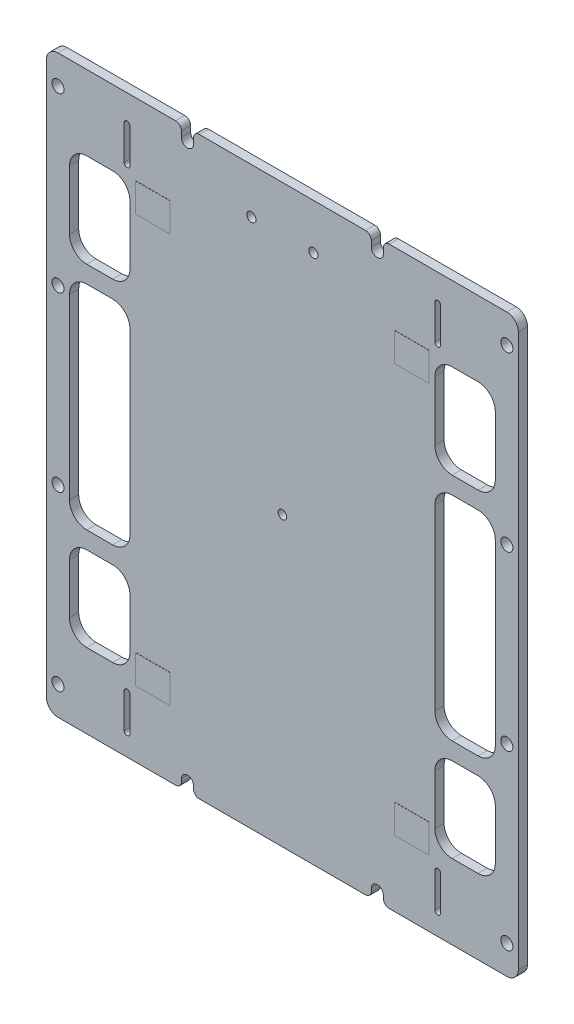
SolidWorks part; units mm, degrees
material "FR4_stuffedProtoboard"
ref_plane "Front Plane" through (0, 0, 0) normal (0, 0, 1) x (1, 0, 0)
ref_plane "Top Plane" through (0, 0, 0) normal (0, 1, 0) x (1, 0, 0)
ref_plane "Right Plane" through (0, 0, 0) normal (1, 0, 0) x (0, 0, -1)
sketch "Sketch1" plane through (0, 0, 0) normal (0, 0, 1) x (1, 0, 0)
  line L1 (-39, -50) -> (39, -50)
  line L2 (-41, -48) -> (-41, 48)
  line L3 (-39, 50) -> (39, 50)
  line L4 (41, -48) -> (41, 48)
  line L5 (-41, -50) -> (41, 50) construction
  line L6 (-41, 50) -> (41, -50) construction
  arc A0 (-39, -50) -> (-41, -48) centre (-39, -48) cw
  arc A1 (39, -50) -> (41, -48) centre (39, -48) ccw
  arc A2 (39, 50) -> (41, 48) centre (39, 48) cw
  arc A3 (-41, 48) -> (-39, 50) centre (-39, 48) cw
  point P0 (0, 0)
  dimension "D3" = 2
  dimension "D1" = 100
  dimension "D2" = 82
extrude "boardOutline" add sketch "Sketch1" along normal blind 1.6
sketch "Sketch2" plane through (0, 0, 1.6) normal (0, 0, 1) x (1, 0, 0)
  line L0 (39, 50) -> (-39, 50) construction
  line L1 (-41, 48) -> (-41, -48) construction
  line L2 (-5.385, 42.1) -> (5.385, 42.1) construction
  line L3 (-37.5, 44.2) -> (-37.5, 4.2) construction
  line L4 (0, 42.1) -> (0, 50) construction
  circle A0 centre (0, 0) radius 0.75
  circle A1 centre (-37.5, 44.2) radius 1.05 construction
  circle A2 centre (37.5, 44.2) radius 1.05 construction
  circle A3 centre (37.5, 4.2) radius 1.05 construction
  circle A4 centre (37.5, -35.8) radius 1.05 construction
  circle A5 centre (-37.5, 4.2) radius 1.05 construction
  circle A6 centre (-37.5, -35.8) radius 1.05 construction
  circle A7 centre (-5.385, 42.1) radius 0.8
  circle A8 centre (5.385, 42.1) radius 0.8
  dimension "D1" = 1.5
  dimension "D2" = 2.1
  dimension "D9" = 10.77
  dimension "D7" = 1.6
  dimension "D11" = 7.9
  dimension "D3" = 5.8
  dimension "D4" = 3.5
  dimension "D8" = 40
  dimension "D10" = 37.5
  dimension "D5" = 2
  dimension "D6" = 3
extrude "componentHoles" cut sketch "Sketch2" against normal through all
sketch "Sketch4" plane through (0, 0, 1.6) normal (0, 0, 1) x (1, 0, 0)
  line L0 (-27, 39.25) -> (-27, 45.25) construction
  line L1 (-27.5, 39.25) -> (-27.5, 45.25)
  line L2 (-26.5, 39.25) -> (-26.5, 45.25)
  line L3 (39, 50) -> (-39, 50) construction
  line L4 (-41, 48) -> (-41, -48) construction
  line L5 (27, 39.25) -> (27, 45.25) construction
  line L6 (26.5, 39.25) -> (26.5, 45.25)
  line L7 (27.5, 39.25) -> (27.5, 45.25)
  line L8 (27, -46.25) -> (27, -40.25) construction
  line L9 (26.5, -46.25) -> (26.5, -40.25)
  line L10 (27.5, -46.25) -> (27.5, -40.25)
  line L11 (-27, -46.25) -> (-27, -40.25) construction
  line L12 (-27.5, -46.25) -> (-27.5, -40.25)
  line L13 (-26.5, -46.25) -> (-26.5, -40.25)
  line L14 (-27, 39.25) -> (27, 39.25) construction
  line L15 (0, 39.25) -> (0, 50) construction
  arc A0 (-27.5, 39.25) -> (-26.5, 39.25) centre (-27, 39.25) ccw
  arc A1 (-26.5, 45.25) -> (-27.5, 45.25) centre (-27, 45.25) ccw
  arc A2 (26.5, 39.25) -> (27.5, 39.25) centre (27, 39.25) ccw
  arc A3 (27.5, 45.25) -> (26.5, 45.25) centre (27, 45.25) ccw
  arc A4 (26.5, -46.25) -> (27.5, -46.25) centre (27, -46.25) ccw
  arc A5 (27.5, -40.25) -> (26.5, -40.25) centre (27, -40.25) ccw
  arc A6 (-27.5, -46.25) -> (-26.5, -46.25) centre (-27, -46.25) ccw
  arc A7 (-26.5, -40.25) -> (-27.5, -40.25) centre (-27, -40.25) ccw
  point P2 (-27, 42.25)
  point P16 (27, 42.25)
  point P23 (27, -43.25)
  point P30 (-27, -43.25)
  dimension "D1" = 4.75
  dimension "D2" = 13.5
  dimension "D3" = 1
  dimension "D4" = 6
  dimension "D7" = 54
  dimension "D9" = 79.5
  dimension "D5" = 2
  dimension "D6" = 2
extrude "solarCellContactHoles" cut sketch "Sketch4" against normal blind 1.6
sketch "Sketch3" plane through (0, 0, 1.6) normal (0, 0, 1) x (1, 0, 0)
  line L1 (-34, 37) -> (-29.5, 37)
  line L2 (-37, 34) -> (-37, 23.7)
  line L3 (-34, 20.7) -> (-29.5, 20.7)
  line L4 (-26.5, 34) -> (-26.5, 23.7)
  line L5 (-41, 48) -> (-41, -48) construction
  line L6 (-29.5, -22.3) -> (-34, -22.3)
  line L9 (0, 50) -> (0, -50) construction
  line L10 (39, 50) -> (-39, 50) construction
  line L11 (-39, -50) -> (39, -50) construction
  line L12 (-26.5, -25.3) -> (-26.5, -34)
  line L13 (-29.5, -37) -> (-34, -37)
  line L14 (-37, -25.3) -> (-37, -34)
  line L19 (-29.5, -19.3) -> (-34, -19.3)
  line L25 (-26.5, -16.3) -> (-26.5, 14.7)
  line L26 (-29.5, 17.7) -> (-34, 17.7)
  line L27 (-37, -16.3) -> (-37, 14.7)
  arc A0 (-37, 23.7) -> (-34, 20.7) centre (-34, 23.7) ccw
  arc A1 (-29.5, 20.7) -> (-26.5, 23.7) centre (-29.5, 23.7) ccw
  arc A2 (-29.5, 37) -> (-26.5, 34) centre (-29.5, 34) cw
  arc A3 (-34, 37) -> (-37, 34) centre (-34, 34) ccw
  arc A4 (-29.5, -19.3) -> (-26.5, -16.3) centre (-29.5, -16.3) ccw
  arc A5 (-26.5, -34) -> (-29.5, -37) centre (-29.5, -34) cw
  arc A6 (-34, -37) -> (-37, -34) centre (-34, -34) cw
  arc A7 (-34, -22.3) -> (-37, -25.3) centre (-34, -25.3) ccw
  arc A8 (-29.5, -22.3) -> (-26.5, -25.3) centre (-29.5, -25.3) cw
  arc A17 (-34, -19.3) -> (-37, -16.3) centre (-34, -16.3) cw
  arc A18 (-34, 17.7) -> (-37, 14.7) centre (-34, 14.7) ccw
  arc A19 (-26.5, 14.7) -> (-29.5, 17.7) centre (-29.5, 14.7) ccw
  point P12 (-26.5, 20.7)
  point P15 (-26.5, 37)
  point P18 (-37, 37)
  dimension "D5" = 3
  dimension "D10" = 13
  dimension "D7" = 3
  dimension "D11" = 3
  dimension "D1" = 10.5
  dimension "D2" = 29.3
  dimension "D3" = 13
  dimension "D4" = 4
  dimension "D8" = 3
  dimension "D9" = 3
  dimension "D6" = 37
extrude "windows_1side" cut sketch "Sketch3" against normal through all
sketch "Sketch5" plane through (0, 0, 1.6) normal (0, 0, 1) x (1, 0, 0)
  line L0 (-41, 48) -> (-41, -48) construction
  line L1 (-25.5, 37.5) -> (-19.5, 37.5)
  line L2 (-25.5, 37.5) -> (-25.5, 32.5)
  line L3 (-25.5, 32.5) -> (-19.5, 32.5)
  line L4 (-19.5, 37.5) -> (-19.5, 32.5)
  line L5 (0, 37.5) -> (0, 50) construction
  line L6 (19.5, 37.5) -> (19.5, 32.5)
  line L7 (25.5, 37.5) -> (25.5, 32.5)
  line L8 (19.5, 32.5) -> (25.5, 32.5)
  line L9 (19.5, 37.5) -> (25.5, 37.5)
  line L10 (19.5, -33.5) -> (19.5, -38.5)
  line L11 (25.5, -33.5) -> (25.5, -38.5)
  line L12 (19.5, -38.5) -> (25.5, -38.5)
  line L13 (19.5, -33.5) -> (25.5, -33.5)
  line L14 (-25.5, -33.5) -> (-25.5, -38.5)
  line L15 (-19.5, -33.5) -> (-19.5, -38.5)
  line L16 (-25.5, -38.5) -> (-19.5, -38.5)
  line L17 (-25.5, -33.5) -> (-19.5, -33.5)
  line L18 (-19.5, 37.5) -> (19.5, 37.5) construction
  line L19 (-25.5, 37.5) -> (-25.5, -33.5) construction
  line L20 (39, 50) -> (-39, 50) construction
  arc A0 (-27.5, 39.25) -> (-26.5, 39.25) centre (-27, 39.25) ccw construction
  dimension "D1" = 5
  dimension "D2" = 6
  dimension "D3" = 15.5
  dimension "D4" = 1.75
  dimension "D7" = 45
  dimension "D8" = 71
  dimension "D5" = 2
  dimension "D6" = 2
extrude "contactPads" add sketch "Sketch5" along normal blind 0.02
hole_wizard "M2 Clearance Hole1" positions "Sketch6" profile "Sketch7" hole size "M2" standard "ANSI Metric" end condition through all
sketch "Sketch6" plane through (0, 0, 0) normal (0, 0, -1) x (-1, 0, 0)
  line L5 (39, -50) -> (39, -45) construction
  line L6 (39, -50) -> (-39, -50) construction
  line L7 (39, -45) -> (39, -15) construction
  line L8 (39, -15) -> (39, 15) construction
  line L9 (39, 15) -> (39, 45) construction
  line L10 (39, 45) -> (39, 50) construction
  line L11 (-39, 50) -> (39, 50) construction
  line L15 (37, -27.0602) -> (41, -27.0602) construction
  line L16 (37, -25.3) -> (37, -34) construction
  line L17 (41, 48) -> (41, -48) construction
  point P0 (39, 45)
  point P27 (39, -15)
  point P36 (39, -45)
  point P38 (39, 15)
  point P73 (39, -27.0602)
  dimension "D2" = 5
sketch "Sketch7" plane through (-39, 45, 0) normal (1, 0, 0) x (0, 1, 0)
  line L0 (0, 0) -> (0, 1.62)
  line L1 (0, 1.62) -> (1.05, 1.62)
  line L2 (1.05, 1.62) -> (1.05, 0)
  line L5 (1.05, 0) -> (0, 0)
  line L11 (0, -6.35) -> (0, 107.95) construction
  dimension "Thru Hole Dia." = 2.1
  dimension "Thru Hole Depth" = 1.62
sketch "Sketch10" plane through (0, 0, 0) normal (0, 0, -1) x (-1, 0, 0)
  line L0 (16.5, 48) -> (16.5, 55.0732) construction
  line L1 (15.45, 48) -> (15.45, 55.0732)
  line L2 (17.55, 48) -> (17.55, 55.0732)
  line L3 (16.5, -48.5) -> (16.5, -55.5732) construction
  line L4 (17.55, -48.5) -> (17.55, -55.5732)
  line L5 (15.45, -48.5) -> (15.45, -55.5732)
  line L6 (41, 48) -> (41, -48) construction
  line L8 (39, -50) -> (-39, -50) construction
  line L9 (-39, 50) -> (39, 50) construction
  arc A0 (15.45, 48) -> (17.55, 48) centre (16.5, 48) ccw
  arc A1 (17.55, 55.0732) -> (15.45, 55.0732) centre (16.5, 55.0732) ccw
  arc A2 (17.55, -48.5) -> (15.45, -48.5) centre (16.5, -48.5) ccw
  arc A3 (15.45, -55.5732) -> (17.55, -55.5732) centre (16.5, -55.5732) ccw
  point P2 (16.5, 51.5366)
  point P7 (16.5, -52.0366)
  dimension "D1" = 1.05
  dimension "D2" = 24.5
  dimension "D3" = 2
  dimension "D4" = 1.5
extrude "Cut-Extrude1" cut sketch "Sketch10" against normal through all both and the other way through all
fillet "Fillet3" radius 1 4 edges at (-17.55, 50, 0.8) (-15.45, 50, 0.8) (-15.45, -50, 0.8) (-17.55, -50, 0.8)
mirror "Mirror1" about plane through (0, 0, 0) normal (1, 0, 0) of "Cut-Extrude1", "Fillet3", "windows_1side", "M2 Clearance Hole1"
sketch "thermalContact" plane through (0, 0, 1.6) normal (0, 0, 1) x (1, 0, 0)
  line L0 (-37, 43) -> (-37, 23.7) construction
  line L1 (-34, 20.7) -> (-21, 20.7) construction
  line L2 (-18, 23.7) -> (-18, 43) construction
  line L3 (-21, 46) -> (-34, 46) construction
  line L4 (-41, 48) -> (-41, -162)
  line L5 (39, 50) -> (-39, 50)
  line L6 (41, -162) -> (41, 48)
  line L7 (-39, -164) -> (39, -164)
  line L8 (-41, 48) -> (-41, -162)
  line L9 (39, 50) -> (-39, 50)
  line L10 (41, -162) -> (41, 48)
  line L11 (-39, -164) -> (39, -164)
  line L12 (-37, 43) -> (-37, 23.7)
  line L13 (-34, 20.7) -> (-21, 20.7)
  line L14 (-18, 23.7) -> (-18, 43)
  line L15 (-21, 46) -> (-34, 46)
  line L16 (18, 43) -> (18, 23.7) construction
  line L17 (21, 20.7) -> (34, 20.7) construction
  line L18 (37, 23.7) -> (37, 43) construction
  line L19 (34, 46) -> (21, 46) construction
  line L20 (18, 43) -> (18, 23.7)
  line L21 (21, 20.7) -> (34, 20.7)
  line L22 (37, 23.7) -> (37, 43)
  line L23 (34, 46) -> (21, 46)
  line L24 (-12, -47) -> (12, -47) construction
  line L25 (15, -44) -> (15, -25.3) construction
  line L26 (12, -22.3) -> (-12, -22.3) construction
  line L27 (-15, -25.3) -> (-15, -44) construction
  line L28 (-12, -47) -> (12, -47)
  line L29 (15, -44) -> (15, -25.3)
  line L30 (12, -22.3) -> (-12, -22.3)
  line L31 (-15, -25.3) -> (-15, -44)
  line L32 (-37, -25.3) -> (-37, -44) construction
  line L33 (-34, -47) -> (-21, -47) construction
  line L34 (-18, -44) -> (-18, -25.3) construction
  line L35 (-21, -22.3) -> (-34, -22.3) construction
  line L36 (-37, -25.3) -> (-37, -44)
  line L37 (-34, -47) -> (-21, -47)
  line L38 (-18, -44) -> (-18, -25.3)
  line L39 (-21, -22.3) -> (-34, -22.3)
  line L40 (18, -25.3) -> (18, -44) construction
  line L41 (21, -47) -> (34, -47) construction
  line L42 (37, -44) -> (37, -25.3) construction
  line L43 (34, -22.3) -> (21, -22.3) construction
  line L44 (18, -25.3) -> (18, -44)
  line L45 (21, -47) -> (34, -47)
  line L46 (37, -44) -> (37, -25.3)
  line L47 (34, -22.3) -> (21, -22.3)
  line L48 (-12, -19.3) -> (12, -19.3) construction
  line L49 (15, -16.3) -> (15, 14.7) construction
  line L50 (12, 17.7) -> (-12, 17.7) construction
  line L51 (-15, 14.7) -> (-15, -16.3) construction
  line L52 (-12, -19.3) -> (12, -19.3)
  line L53 (15, -16.3) -> (15, 14.7)
  line L54 (12, 17.7) -> (-12, 17.7)
  line L55 (-15, 14.7) -> (-15, -16.3)
  line L56 (-21, 17.7) -> (-34, 17.7) construction
  line L57 (-37, 14.7) -> (-37, -16.3) construction
  line L58 (-34, -19.3) -> (-21, -19.3) construction
  line L59 (-18, -16.3) -> (-18, 14.7) construction
  line L60 (-21, 17.7) -> (-34, 17.7)
  line L61 (-37, 14.7) -> (-37, -16.3)
  line L62 (-34, -19.3) -> (-21, -19.3)
  line L63 (-18, -16.3) -> (-18, 14.7)
  line L64 (21, -19.3) -> (34, -19.3) construction
  line L65 (37, -16.3) -> (37, 14.7) construction
  line L66 (34, 17.7) -> (21, 17.7) construction
  line L67 (18, 14.7) -> (18, -16.3) construction
  line L68 (21, -19.3) -> (34, -19.3)
  line L69 (37, -16.3) -> (37, 14.7)
  line L70 (34, 17.7) -> (21, 17.7)
  line L71 (18, 14.7) -> (18, -16.3)
  line L72 (-12, 20.7) -> (12, 20.7) construction
  line L73 (15, 23.7) -> (15, 43) construction
  line L74 (12, 46) -> (-12, 46) construction
  line L75 (-15, 43) -> (-15, 23.7) construction
  line L76 (-12, 20.7) -> (12, 20.7)
  line L77 (15, 23.7) -> (15, 43)
  line L78 (12, 46) -> (-12, 46)
  line L79 (-15, 43) -> (-15, 23.7)
  line L80 (-21, -50) -> (-34, -50) construction
  line L81 (-37, -53) -> (-37, -61) construction
  line L82 (-34, -64) -> (-21, -64) construction
  line L83 (-18, -61) -> (-18, -53) construction
  line L84 (-21, -50) -> (-34, -50)
  line L85 (-37, -53) -> (-37, -61)
  line L86 (-34, -64) -> (-21, -64)
  line L87 (-18, -61) -> (-18, -53)
  line L88 (-15, -53) -> (-15, -61) construction
  line L89 (-12, -64) -> (12, -64) construction
  line L90 (15, -61) -> (15, -53) construction
  line L91 (12, -50) -> (-12, -50) construction
  line L92 (-15, -53) -> (-15, -61)
  line L93 (-12, -64) -> (12, -64)
  line L94 (15, -61) -> (15, -53)
  line L95 (12, -50) -> (-12, -50)
  line L96 (18, -53) -> (18, -61) construction
  line L97 (21, -64) -> (34, -64) construction
  line L98 (37, -61) -> (37, -53) construction
  line L99 (34, -50) -> (21, -50) construction
  line L100 (18, -53) -> (18, -61)
  line L101 (21, -64) -> (34, -64)
  line L102 (37, -61) -> (37, -53)
  line L103 (34, -50) -> (21, -50)
  arc A0 (-34, 46) -> (-37, 43) centre (-34, 43) ccw construction
  arc A1 (-37, 23.7) -> (-34, 20.7) centre (-34, 23.7) ccw construction
  arc A2 (-21, 20.7) -> (-18, 23.7) centre (-21, 23.7) ccw construction
  arc A3 (-18, 43) -> (-21, 46) centre (-21, 43) ccw construction
  arc A4 (-39, 50) -> (-41, 48) centre (-39, 48) ccw
  arc A5 (41, 48) -> (39, 50) centre (39, 48) ccw
  arc A6 (39, -164) -> (41, -162) centre (39, -162) ccw
  arc A7 (-41, -162) -> (-39, -164) centre (-39, -162) ccw
  arc A8 (-39, 50) -> (-41, 48) centre (-39, 48) ccw
  arc A9 (41, 48) -> (39, 50) centre (39, 48) ccw
  arc A10 (39, -164) -> (41, -162) centre (39, -162) ccw
  arc A11 (-41, -162) -> (-39, -164) centre (-39, -162) ccw
  arc A12 (-34, 46) -> (-37, 43) centre (-34, 43) ccw
  arc A13 (-37, 23.7) -> (-34, 20.7) centre (-34, 23.7) ccw
  arc A14 (-21, 20.7) -> (-18, 23.7) centre (-21, 23.7) ccw
  arc A15 (-18, 43) -> (-21, 46) centre (-21, 43) ccw
  arc A16 (21, 46) -> (18, 43) centre (21, 43) ccw construction
  arc A17 (18, 23.7) -> (21, 20.7) centre (21, 23.7) ccw construction
  arc A18 (34, 20.7) -> (37, 23.7) centre (34, 23.7) ccw construction
  arc A19 (37, 43) -> (34, 46) centre (34, 43) ccw construction
  arc A20 (21, 46) -> (18, 43) centre (21, 43) ccw
  arc A21 (18, 23.7) -> (21, 20.7) centre (21, 23.7) ccw
  arc A22 (34, 20.7) -> (37, 23.7) centre (34, 23.7) ccw
  arc A23 (37, 43) -> (34, 46) centre (34, 43) ccw
  arc A24 (-15, -44) -> (-12, -47) centre (-12, -44) ccw construction
  arc A25 (12, -47) -> (15, -44) centre (12, -44) ccw construction
  arc A26 (15, -25.3) -> (12, -22.3) centre (12, -25.3) ccw construction
  arc A27 (-12, -22.3) -> (-15, -25.3) centre (-12, -25.3) ccw construction
  arc A28 (-15, -44) -> (-12, -47) centre (-12, -44) ccw
  arc A29 (12, -47) -> (15, -44) centre (12, -44) ccw
  arc A30 (15, -25.3) -> (12, -22.3) centre (12, -25.3) ccw
  arc A31 (-12, -22.3) -> (-15, -25.3) centre (-12, -25.3) ccw
  arc A32 (-34, -22.3) -> (-37, -25.3) centre (-34, -25.3) ccw construction
  arc A33 (-37, -44) -> (-34, -47) centre (-34, -44) ccw construction
  arc A34 (-21, -47) -> (-18, -44) centre (-21, -44) ccw construction
  arc A35 (-18, -25.3) -> (-21, -22.3) centre (-21, -25.3) ccw construction
  arc A36 (-34, -22.3) -> (-37, -25.3) centre (-34, -25.3) ccw
  arc A37 (-37, -44) -> (-34, -47) centre (-34, -44) ccw
  arc A38 (-21, -47) -> (-18, -44) centre (-21, -44) ccw
  arc A39 (-18, -25.3) -> (-21, -22.3) centre (-21, -25.3) ccw
  arc A40 (21, -22.3) -> (18, -25.3) centre (21, -25.3) ccw construction
  arc A41 (18, -44) -> (21, -47) centre (21, -44) ccw construction
  arc A42 (34, -47) -> (37, -44) centre (34, -44) ccw construction
  arc A43 (37, -25.3) -> (34, -22.3) centre (34, -25.3) ccw construction
  arc A44 (21, -22.3) -> (18, -25.3) centre (21, -25.3) ccw
  arc A45 (18, -44) -> (21, -47) centre (21, -44) ccw
  arc A46 (34, -47) -> (37, -44) centre (34, -44) ccw
  arc A47 (37, -25.3) -> (34, -22.3) centre (34, -25.3) ccw
  arc A48 (-15, -16.3) -> (-12, -19.3) centre (-12, -16.3) ccw construction
  arc A49 (12, -19.3) -> (15, -16.3) centre (12, -16.3) ccw construction
  arc A50 (15, 14.7) -> (12, 17.7) centre (12, 14.7) ccw construction
  arc A51 (-12, 17.7) -> (-15, 14.7) centre (-12, 14.7) ccw construction
  arc A52 (-15, -16.3) -> (-12, -19.3) centre (-12, -16.3) ccw
  arc A53 (12, -19.3) -> (15, -16.3) centre (12, -16.3) ccw
  arc A54 (15, 14.7) -> (12, 17.7) centre (12, 14.7) ccw
  arc A55 (-12, 17.7) -> (-15, 14.7) centre (-12, 14.7) ccw
  arc A56 (-18, 14.7) -> (-21, 17.7) centre (-21, 14.7) ccw construction
  arc A57 (-34, 17.7) -> (-37, 14.7) centre (-34, 14.7) ccw construction
  arc A58 (-37, -16.3) -> (-34, -19.3) centre (-34, -16.3) ccw construction
  arc A59 (-21, -19.3) -> (-18, -16.3) centre (-21, -16.3) ccw construction
  arc A60 (-18, 14.7) -> (-21, 17.7) centre (-21, 14.7) ccw
  arc A61 (-34, 17.7) -> (-37, 14.7) centre (-34, 14.7) ccw
  arc A62 (-37, -16.3) -> (-34, -19.3) centre (-34, -16.3) ccw
  arc A63 (-21, -19.3) -> (-18, -16.3) centre (-21, -16.3) ccw
  arc A64 (18, -16.3) -> (21, -19.3) centre (21, -16.3) ccw construction
  arc A65 (34, -19.3) -> (37, -16.3) centre (34, -16.3) ccw construction
  arc A66 (37, 14.7) -> (34, 17.7) centre (34, 14.7) ccw construction
  arc A67 (21, 17.7) -> (18, 14.7) centre (21, 14.7) ccw construction
  arc A68 (18, -16.3) -> (21, -19.3) centre (21, -16.3) ccw
  arc A69 (34, -19.3) -> (37, -16.3) centre (34, -16.3) ccw
  arc A70 (37, 14.7) -> (34, 17.7) centre (34, 14.7) ccw
  arc A71 (21, 17.7) -> (18, 14.7) centre (21, 14.7) ccw
  arc A72 (-15, 23.7) -> (-12, 20.7) centre (-12, 23.7) ccw construction
  arc A73 (12, 20.7) -> (15, 23.7) centre (12, 23.7) ccw construction
  arc A74 (15, 43) -> (12, 46) centre (12, 43) ccw construction
  arc A75 (-12, 46) -> (-15, 43) centre (-12, 43) ccw construction
  arc A76 (-15, 23.7) -> (-12, 20.7) centre (-12, 23.7) ccw
  arc A77 (12, 20.7) -> (15, 23.7) centre (12, 23.7) ccw
  arc A78 (15, 43) -> (12, 46) centre (12, 43) ccw
  arc A79 (-12, 46) -> (-15, 43) centre (-12, 43) ccw
  arc A80 (-34, -50) -> (-37, -53) centre (-34, -53) ccw construction
  arc A81 (-37, -61) -> (-34, -64) centre (-34, -61) ccw construction
  arc A82 (-21, -64) -> (-18, -61) centre (-21, -61) ccw construction
  arc A83 (-18, -53) -> (-21, -50) centre (-21, -53) ccw construction
  arc A84 (-34, -50) -> (-37, -53) centre (-34, -53) ccw
  arc A85 (-37, -61) -> (-34, -64) centre (-34, -61) ccw
  arc A86 (-21, -64) -> (-18, -61) centre (-21, -61) ccw
  arc A87 (-18, -53) -> (-21, -50) centre (-21, -53) ccw
  arc A88 (-15, -61) -> (-12, -64) centre (-12, -61) ccw construction
  arc A89 (12, -64) -> (15, -61) centre (12, -61) ccw construction
  arc A90 (15, -53) -> (12, -50) centre (12, -53) ccw construction
  arc A91 (-12, -50) -> (-15, -53) centre (-12, -53) ccw construction
  arc A92 (-15, -61) -> (-12, -64) centre (-12, -61) ccw
  arc A93 (12, -64) -> (15, -61) centre (12, -61) ccw
  arc A94 (15, -53) -> (12, -50) centre (12, -53) ccw
  arc A95 (-12, -50) -> (-15, -53) centre (-12, -53) ccw
  arc A96 (21, -50) -> (18, -53) centre (21, -53) ccw construction
  arc A97 (18, -61) -> (21, -64) centre (21, -61) ccw construction
  arc A98 (34, -64) -> (37, -61) centre (34, -61) ccw construction
  arc A99 (37, -53) -> (34, -50) centre (34, -53) ccw construction
  arc A100 (18, -61) -> (21, -64) centre (21, -61) ccw
  arc A101 (34, -64) -> (37, -61) centre (34, -61) ccw
  arc A102 (37, -53) -> (34, -50) centre (34, -53) ccw
  arc A103 (21, -50) -> (18, -53) centre (21, -53) ccw
  dimension "D1" = 0
